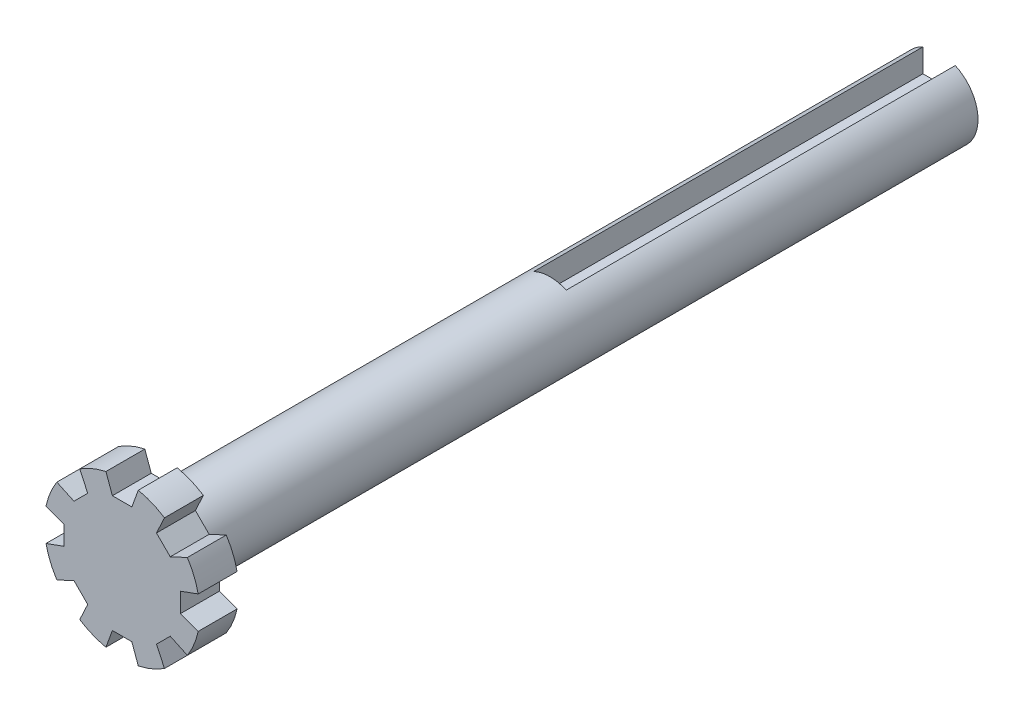
SolidWorks part; units mm, degrees
ref_plane "前视基准面" through (0, 0, 0) normal (0, 0, 1) x (1, 0, 0)
ref_plane "上视基准面" through (0, 0, 0) normal (0, 1, 0) x (1, 0, 0)
ref_plane "右视基准面" through (0, 0, 0) normal (1, 0, 0) x (0, 0, -1)
sketch "Sketch1" plane through (0, 0, 0) normal (0, 0, 1) x (1, 0, 0)
  line L0 (0.208, 0.9781) -> (0.125, 0.75)
  line L1 (0.125, 0.75) -> (-0.125, 0.75)
  line L2 (-0.125, 0.75) -> (-0.208, 0.9781)
  line L3 (0, 0.989) -> (0, 0) construction
  line L4 (0.208, 0.4547) -> (0.208, 0.1547)
  line L5 (0.208, 0.1547) -> (-0.208, 0.1547)
  line L6 (-0.208, 0.1547) -> (-0.208, 0.4547)
  arc A0 (-0.208, 0.4547) -> (0.208, 0.4547) centre (0, 0) ccw
  circle A1 centre (0, 0) radius 1
  circle A2 centre (0, 0) radius 0.5
  dimension "D1" = 0.25
  dimension "D5" = 2
  dimension "D6" = 1
  dimension "D2" = 20
  dimension "D3" = 20
  dimension "D4" = 0.75
  dimension "D7" = 0.3
  dimension "D8" = 0.4161
extrude "Base" add sketch "Sketch1" along normal blind 0.5 contours A1
extrude "Cut-Extrude6" cut sketch "Sketch1<3>" against normal through all and the other way through all contours A1 L3 L1 L0 | L3 A1 L2 L1 region at (0.162, 0.8657, 0)
sketch "Sketch1<3>" plane through (0, 0, 0) normal (0, 0, 1) x (1, 0, 0) same geometry as "Sketch1"
pattern_circular "CirPattern1" count 8 over 360 about axis through (0, 0, 0.5) along (0, 0, -1) of "Cut-Extrude6"
extrude "Whole-connection" add sketch "Sketch1<5>" against normal blind 10 contours A0 L4 L5 L6
sketch "Sketch1<5>" plane through (0, 0, 0) normal (0, 0, 1) x (1, 0, 0) same geometry as "Sketch1"
extrude "On-bearing" add sketch "Sketch1<6>" against normal blind 5 contours A2
sketch "Sketch1<6>" plane through (0, 0, 0) normal (0, 0, 1) x (1, 0, 0) same geometry as "Sketch1"
